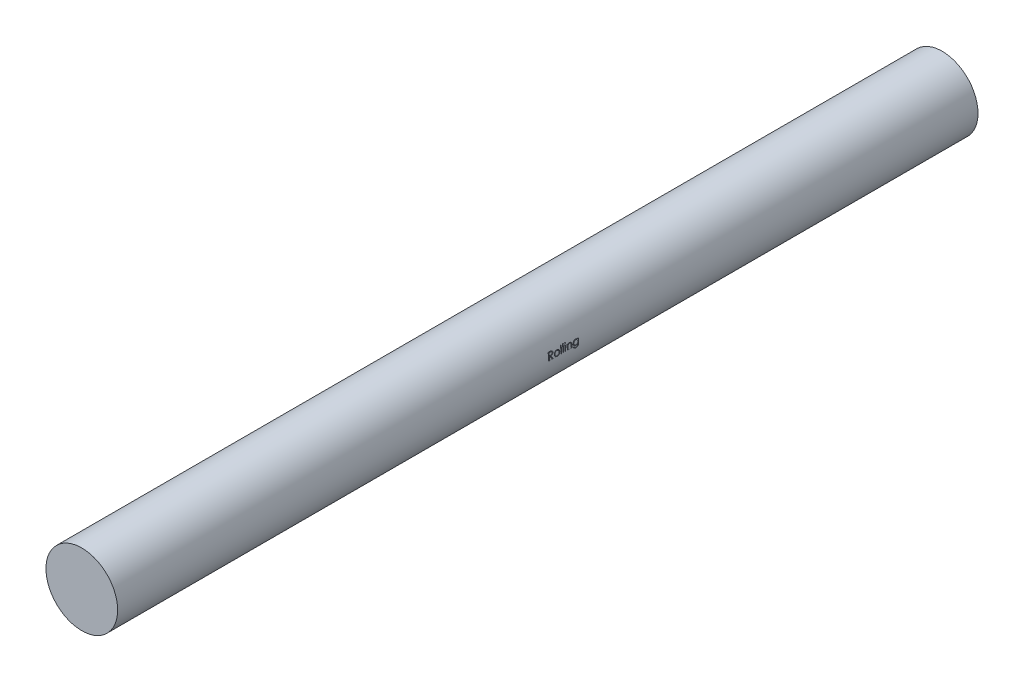
SolidWorks part; units mm, degrees
ref_plane "Front Plane" through (0, 0, 0) normal (0, 0, 1) x (1, 0, 0)
ref_plane "Top Plane" through (0, 0, 0) normal (0, 1, 0) x (1, 0, 0)
ref_plane "Right Plane" through (0, 0, 0) normal (1, 0, 0) x (0, 0, -1)
sketch "Sketch1" plane through (0, 0, 0) normal (0, 0, 1) x (1, 0, 0)
  circle A0 centre (0, 0) radius 50
  dimension "D1" = 100
extrude "Boss-Extrude1" add sketch "Sketch1" along normal mid plane 1200
sketch "Sketch3" plane through (0, 0, 0) normal (1, 0, 0) x (0, 0, -1)
  text T0 "Rolling" font "Century Gothic" height 10
extrude "Cut-Extrude1" cut sketch "Sketch3" along normal through all both and the other way through all
